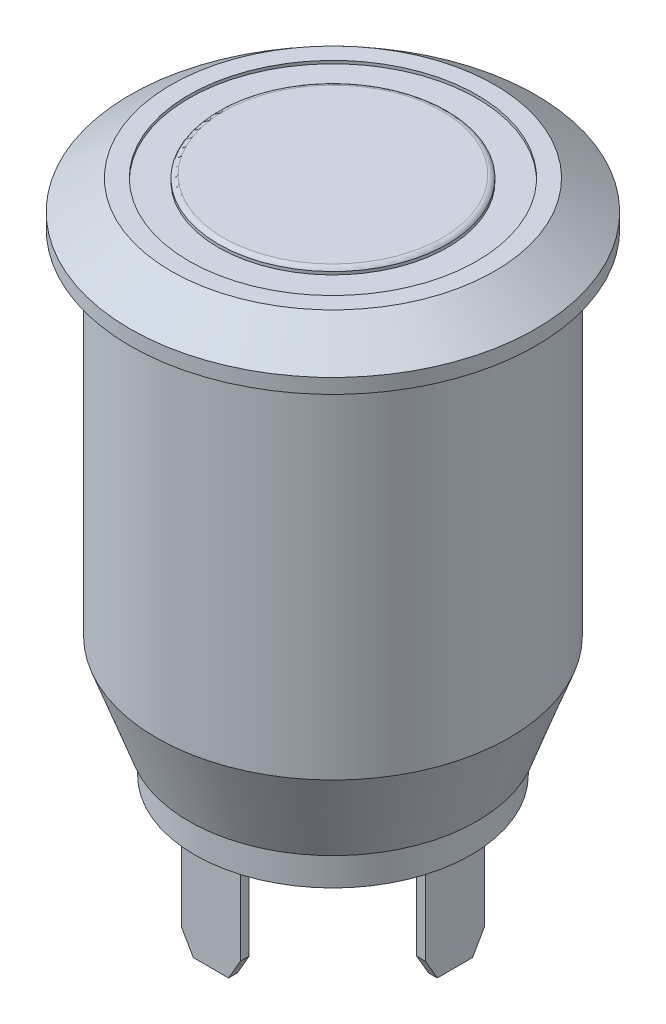
SolidWorks part; units mm, degrees
ref_plane "Front Plane" through (0, 0, 0) normal (0, 0, 1) x (1, 0, 0)
ref_plane "Top Plane" through (0, 0, 0) normal (0, 1, 0) x (1, 0, 0)
ref_plane "Right Plane" through (0, 0, 0) normal (1, 0, 0) x (0, 0, -1)
sketch "Sketch1" plane through (0, 0, 0) normal (1, 0, 0) x (0, 0, -1)
  line L1 (0, 1.6) -> (-3.9, 1.6)
  line L2 (-3.9, 1.6) -> (-3.9, 1.5)
  line L3 (-3.9, 1.5) -> (-5.5, 1.5)
  line L4 (-5.5, 1.5) -> (-6.9, 0.5)
  line L5 (-6.9, 0.5) -> (-6.9, 0)
  line L6 (-6.9, 0) -> (-6, 0)
  line L7 (-6, 0) -> (-6, -15)
  line L8 (-6, -15) -> (-4.7, -15)
  line L9 (-4.7, -15) -> (-4.7, -16.1)
  line L10 (-4.7, -16.1) -> (0, -16.1)
  line L11 (0, 14.375) -> (0, -32.104) construction
  line L12 (0, 1.6) -> (0, -16.1)
  dimension "D1" = 7.8
  dimension "D2" = 13.8
  dimension "D3" = 12
  dimension "D4" = 9.4
  dimension "D5" = 17.6
  dimension "D6" = 16.5
  dimension "D7" = 1.5
  dimension "D8" = 11
  dimension "D9" = 0.5
  dimension "D10" = 0.1
revolve "Revolve1" add sketch "Sketch1" angle 360 about L11
fillet "Fillet1" radius 0.2 1 edges at (0, 1.6, 3.9)
sketch "Sketch2" plane through (0, 1.5, 0) normal (0, 1, 0) x (1, 0, 0)
  circle A0 centre (0, 0) radius 3.9
  circle A1 centre (0, 0) radius 4.9
  circle A3 centre (0, 0) radius 3.9 construction
  dimension "D1" = 9.8
extrude "Cut-Extrude1" cut sketch "Sketch2" against normal blind 0.1
sketch "Sketch3" plane through (0, -16.1, 0) normal (0, -1, 0) x (1, 0, 0)
  line L0 (-1, 4) -> (1, 4)
  line L1 (-1, -4) -> (1, -4)
  line L2 (-1, 4) -> (1, -4) construction
  line L3 (-4, 1) -> (-4, -1)
  line L4 (4, -1) -> (4, 1)
  line L5 (-4, 0) -> (0, 0) construction
  point P12 (4, 0)
  dimension "D1" = 8
  dimension "D2" = 2
  dimension "D3" = 8
  dimension "D4" = 0
  dimension "D5" = 4
extrude "Extrude-Thin1" add sketch "Sketch3" along normal blind 3.6 thin thin type mid plane wall 0.3
chamfer "Chamfer1" distance 0.4 angle 60 8 edges at (1, -19.7, 4) (-1, -19.7, 4) (-4, -19.7, 1) (-4, -19.7, -1) (-1, -19.7, -4) (1, -19.7, -4) (4, -19.7, -1) (4, -19.7, 1) first distance on face at (0, -19.7, 4) first distance on face at (-4, -19.7, 0) first distance on face at (0, -19.7, -4) first distance on face at (4, -19.7, 0)
chamfer "Chamfer2" distance 3 angle 20 1 edges at (0, -15, 6) first distance on face at (0, -15, 6)
